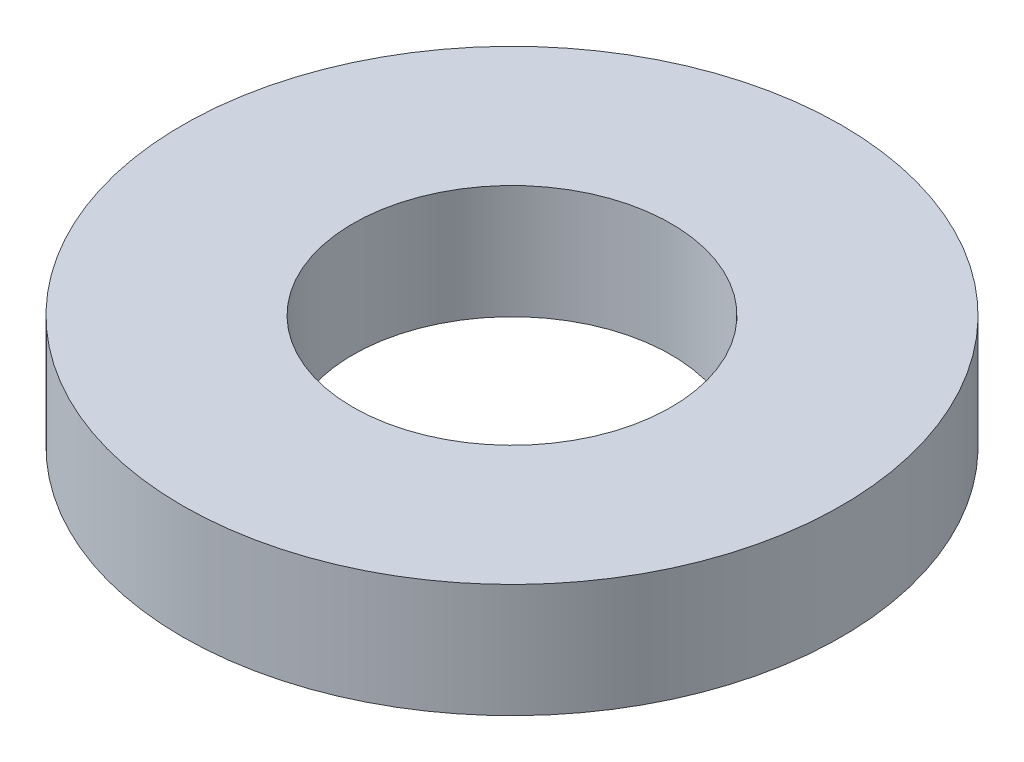
SolidWorks part; units mm, degrees
ref_plane "Front Plane" through (0, 0, 0) normal (0, 0, 1) x (1, 0, 0)
ref_plane "Top Plane" through (0, 0, 0) normal (0, 1, 0) x (1, 0, 0)
ref_plane "Right Plane" through (0, 0, 0) normal (1, 0, 0) x (0, 0, -1)
sketch "Sketch1" plane through (0, 0, 0) normal (0, 1, 0) x (1, 0, 0)
  circle A0 centre (0, 0) radius 72.5
  dimension "FLANGE_OD" = 145
extrude "Boss-Extrude1" add sketch "Sketch1" along normal blind 25
sketch "Sketch2" plane through (0, 0, 0) normal (0, 1, 0) x (1, 0, 0)
  circle A0 centre (0, 0) radius 35
  dimension "BORE_D" = 70
extrude "Cut-Extrude1" cut sketch "Sketch2" along normal through all
sketch "Sketch3" plane through (0, 25, 0) normal (0, 1, 0) x (1, 0, 0)
  circle A0 centre (0, 0) radius 29.9233 construction
  circle A1 centre (-29.9233, 0) radius 2.7892
  dimension "BOLT_D" = 5.5784
  dimension "BOLT_PCD" = 59.8466
extrude "Cut-Extrude2" cut sketch "Sketch3" against normal blind 24.8681 rebuild error yes
pattern_circular "CirPattern1" count 8 over 360 rebuild error yes
